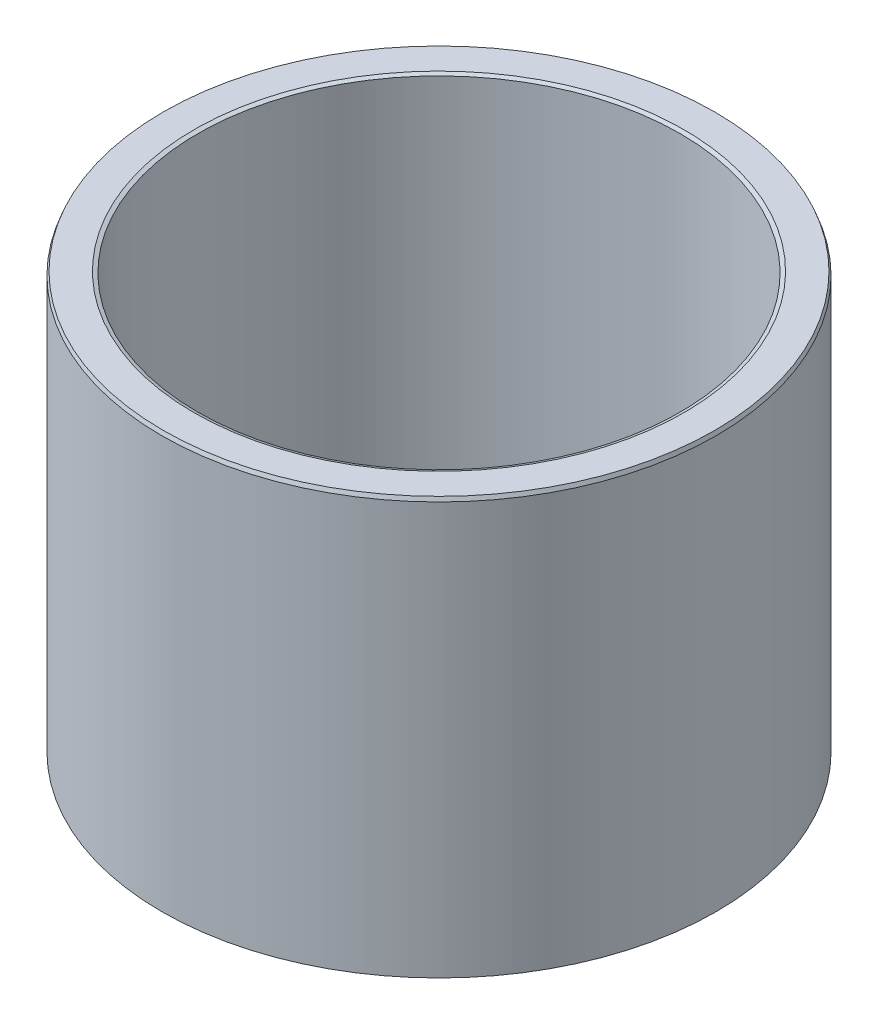
SolidWorks part; units mm, degrees
ref_plane "Front Plane" through (0, 0, 0) normal (0, 0, 1) x (1, 0, 0)
ref_plane "Top Plane" through (0, 0, 0) normal (0, 1, 0) x (1, 0, 0)
ref_plane "Right Plane" through (0, 0, 0) normal (1, 0, 0) x (0, 0, -1)
sketch "Sketch1" plane through (0, 0, 0) normal (0, 1, 0) x (1, 0, 0)
  circle A0 centre (0, 0) radius 47.5
  dimension "SLEEVE_OD" = 95
extrude "Boss-Extrude1" add sketch "Sketch1" along normal blind 71.5364
sketch "Sketch2" plane through (0, 0, 0) normal (0, 1, 0) x (1, 0, 0)
  circle A0 centre (0, 0) radius 41.3262
  dimension "BORE_D" = 82.6524
extrude "Cut-Extrude1" cut sketch "Sketch2" along normal through all
chamfer "Chamfer1" distance 0.6603 angle 20.745 4 edges at (0, 71.5364, 41.3262) (0, 0, 41.3262) (0, 0, 47.5) (0, 71.5364, 47.5) first distance on face at (0, 71.5364, 41.3262) first distance on face at (0, 0, 41.3262) first distance on face at (0, 71.5364, 47.5)
